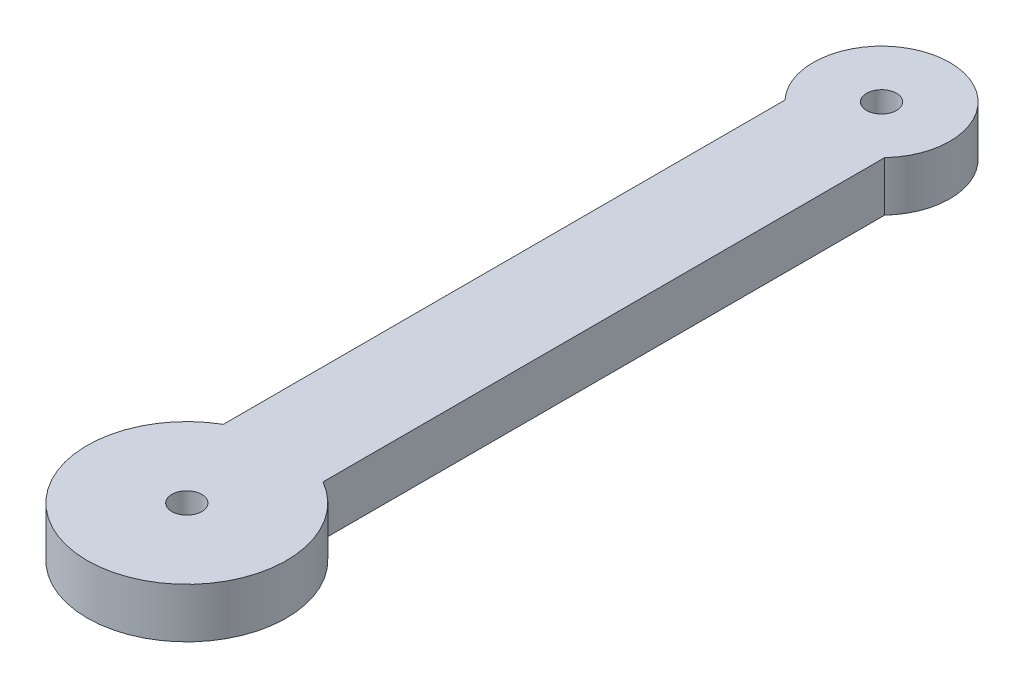
SolidWorks part; units mm, degrees
ref_plane "Front Plane" through (0, 0, 0) normal (0, 0, 1) x (1, 0, 0)
ref_plane "Top Plane" through (0, 0, 0) normal (0, 1, 0) x (1, 0, 0)
ref_plane "Right Plane" through (0, 0, 0) normal (1, 0, 0) x (0, 0, -1)
sketch "Sketch2" plane through (0, 0, 0) normal (0, 1, 0) x (1, 0, 0)
  line L0 (-2.5, 32.5) -> (-2.5, 4.3301)
  line L1 (2.5, 32.5) -> (2.5, 4.3301)
  circle A0 centre (0, 0) radius 0.75
  arc A1 (-2.5, 4.3301) -> (2.5, 4.3301) centre (0, 0) ccw
  circle A2 centre (0, 34.8428) radius 0.75
  arc A3 (2.5, 32.5) -> (-2.5, 32.5) centre (0, 34.8428) ccw
  dimension "D1" = 1.5
  dimension "D2" = 5
  dimension "D3" = 3.4261
  dimension "D4" = 2.5
  dimension "D5" = 32.5
extrude "Boss-Extrude1" add sketch "Sketch2" along normal blind 2.5
